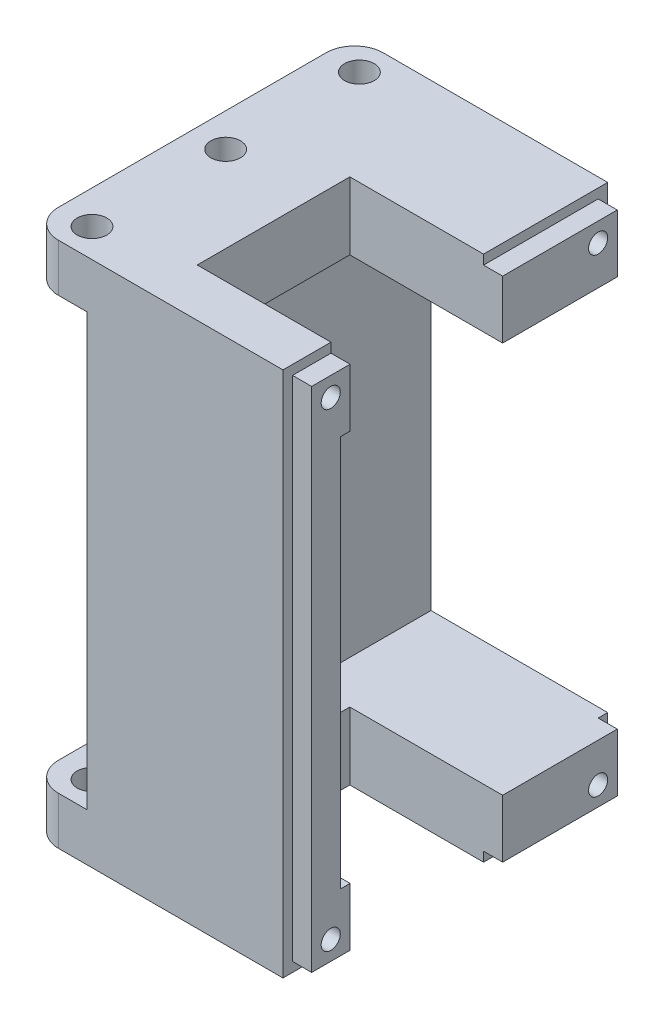
SolidWorks part; units mm, degrees
ref_plane "前视基准面" through (0, 0, 0) normal (0, 0, 1) x (1, 0, 0)
ref_plane "上视基准面" through (0, 0, 0) normal (0, 1, 0) x (1, 0, 0)
ref_plane "右视基准面" through (0, 0, 0) normal (1, 0, 0) x (0, 0, -1)
other "Configuration Table"
sketch "草图1" plane through (0, 0, 0) normal (0, 0, 1) x (1, 0, 0)
  line L0 (-1000, 0) -> (49000, 0) construction
  line L1 (-10.25, -20) -> (10.25, -20)
  line L2 (-10.25, -20) -> (-10.25, 20)
  line L3 (-10.25, 20) -> (10.25, 20)
  line L4 (10.25, -20) -> (10.25, 20)
  line L5 (-10.25, -20) -> (10.25, 20) construction
  line L6 (-10.25, 20) -> (10.25, -20) construction
  line L7 (-5, 15) -> (5, 15)
  line L8 (-5, 15) -> (-5, 25)
  line L9 (-5, 25) -> (5, 25)
  line L10 (5, 15) -> (5, 25)
  line L11 (-5, 15) -> (5, 25) construction
  line L12 (-5, 25) -> (5, 15) construction
  line L14 (-10.25, -35.1417) -> (10.25, -35.1417)
  line L15 (-10.25, -35.1417) -> (-10.25, 35.1417)
  line L16 (-10.25, 35.1417) -> (10.25, 35.1417)
  line L17 (10.25, -35.1417) -> (10.25, 35.1417)
  line L18 (-10.25, -35.1417) -> (10.25, 35.1417) construction
  line L19 (-10.25, 35.1417) -> (10.25, -35.1417) construction
  circle A0 centre (-5, 25) radius 2
  circle A1 centre (5, 25) radius 2
  circle A2 centre (5, -25) radius 2
  circle A3 centre (-5, -25) radius 2
  point P0 (0, 0)
  point P6 (0, 20)
  point P19 (0, 0)
  dimension "D5" = 4
  dimension "D6" = 4
  dimension "D1" = 20.5
  dimension "D2" = 40
  dimension "D3" = 10
  dimension "D4" = 10
extrude "凸台-拉伸1" add sketch "草图1" along normal blind 29 contours A1 L10 L3 L17 L16 L15 L8 A0 L9 | L14 L17 L1 L15 A2 A3 | A1 L9 A0 L8 L3 L10 region at (0, -27.7973, 0) region at (0, 28.799, 0) region at (0, 22.2627, 0)
sketch "草图2" plane through (0, 0, 29) normal (0, 0, 1) x (1, 0, 0)
  line L1 (-10.25, 35.1417) -> (10.25, 35.1417)
  line L2 (-10.25, 35.1417) -> (-10.25, -35.1417)
  line L3 (-10.25, -35.1417) -> (10.25, -35.1417)
  line L4 (10.25, 35.1417) -> (10.25, -35.1417)
extrude "凸台-拉伸2" add sketch "草图2" along normal blind 3
sketch "草图3" plane through (0, 0, 0) normal (0, 0, -1) x (-1, 0, 0)
  line L0 (-10.25, -35.1417) -> (-10.25, -20) construction
  line L1 (-10.25, -27.5709) -> (10.25, -27.5709)
  line L2 (-10.25, -27.5709) -> (-10.25, 27.5709)
  line L3 (-10.25, 27.5709) -> (10.25, 27.5709)
  line L4 (10.25, -27.5709) -> (10.25, 27.5709)
  line L5 (10.25, 20) -> (10.25, 35.1417) construction
  line L7 (-10.25, -35.1417) -> (10.25, -35.1417)
  line L8 (-10.25, -35.1417) -> (-10.25, 35.1417)
  line L9 (-10.25, 35.1417) -> (10.25, 35.1417)
  line L10 (10.25, -35.1417) -> (10.25, 35.1417)
  line M2 (-10.25, -35.1417) -> (10.25, -35.1417)
  line M3 (10.25, -35.1417) -> (10.25, -20)
  line M5 (-10.25, -20) -> (-10.25, -35.1417)
extrude "切除-拉伸1" cut sketch "草图3" against normal through all contours L1 M5 M2 M3 | L3 L10 L9 L8 region at (0, -31.3563, 0) region at (0, 31.3563, 0)
sketch "草图5" plane through (0, -27.5709, 0) normal (0, -1, 0) x (1, 0, 0)
  line L0 (0, 0) -> (0, 2.5)
  circle A0 centre (0, 2.5) radius 2.5
  dimension "D2" = 5
  dimension "D1" = 2.5
extrude "凸台-拉伸3" add sketch "草图5" along normal blind 10 contours A0 region at (1.7178, -27.5709, 0.7822)
sketch "草图8" plane through (0, 27.5709, 0) normal (0, 1, 0) x (1, 0, 0)
  line L0 (0, 0) -> (0, -2.5)
  line L1 (0, -2.5) -> (0, -16.5)
  line L2 (0, -16.5) -> (0, -26.5)
  circle A0 centre (0, -16.5) radius 1.6
  circle A1 centre (0, -26.5) radius 1.6
  dimension "D4" = 3.2
  dimension "D5" = 3.2
  dimension "D1" = 2.5
  dimension "D2" = 14
  dimension "D3" = 10
extrude "切除-拉伸2" cut sketch "草图8" against normal up to next contours L1 A0 L2 | L2 A0 L1 | A1 region at (0.6791, 27.5709, 16.5) region at (1.0994, 27.5709, 25.4006) region at (-0.6791, 27.5709, 16.5)
sketch "草图9" plane through (0, -27.5709, 0) normal (0, -1, 0) x (1, 0, 0)
  line L1 (-10.25, 32) -> (10.25, 32)
  line L2 (-10.25, 32) -> (-10.25, 0)
  line L3 (-10.25, 0) -> (10.25, 0)
  line L4 (10.25, 32) -> (10.25, 0)
extrude "切除-拉伸3" cut sketch "草图9" along normal through all
sketch "草图12" plane through (0, 0, 0) normal (0, 0, -1) x (-1, 0, 0)
  line L1 (-10.25, 27.5709) -> (10.25, 27.5709)
  line L2 (-10.25, 27.5709) -> (-10.25, 20)
  line L3 (-10.25, 20) -> (10.25, 20)
  line L4 (10.25, 27.5709) -> (10.25, 20)
  circle A0 centre (-5, 25) radius 2
  circle A1 centre (5, 25) radius 2
extrude "凸台-拉伸5" add sketch "草图12" against normal blind 30
sketch "草图13" plane through (0, 27.5709, 0) normal (0, 1, 0) x (1, 0, 0)
  line L0 (0, 0) -> (0, -32)
  line L1 (10.25, -32) -> (-10.25, -32) construction
  line L2 (0, 0) -> (0, -10)
  line L3 (0, 0) -> (0, -2.5275)
  line L4 (0, 0) -> (0, -5)
  circle A2 centre (0, -5) radius 2.5
  circle A3 centre (0, -5) radius 4
  dimension "D3" = 5
  dimension "D4" = 5
  dimension "D5" = 8
  dimension "D1" = 32
  dimension "D2" = 10
extrude "凸台-拉伸6" add sketch "草图13" along normal blind 10 contours L4 A3 L2 A2 | L2 A3 L4 A2 region at (-2.5894, 27.5709, 5) region at (0.0894, 27.5709, 1.75)
sketch "草图15" plane through (0, 0, 0) normal (1, 0, 0) x (0, 0, -1)
  line L0 (-1, 27.5709) -> (0, 27.5709)
  line L1 (-1, 27.5709) -> (-1, 28.676)
  line L2 (-1, 27.5709) -> (-1, 37.5709) construction
  line L3 (-5, -962.4291) -> (-5, 49037.5709) construction
  line L4 (-2.5, 37.5709) -> (-7.5, 37.5709) construction
  arc A0 (-1, 28.676) -> (0, 27.5709) centre (0.1107, 28.676) ccw
  point P13 (-5, 37.5709)
revolve "旋转1" add sketch "草图15" angle 360 about L3
ref_plane "基准面1" through (0, 0, 5) normal (0, 0, 1) x (1, 0, 0)
sketch "草图16" plane through (0, 0, 5) normal (0, 0, 1) x (1, 0, 0)
  line L0 (0, 37.5709) -> (0, 33.5709)
  line L1 (2.5, 37.5709) -> (-2.5, 37.5709) construction
  circle A0 centre (0, 33.5709) radius 1.5
  dimension "D2" = 3
  dimension "D1" = 4
extrude "切除-拉伸5" cut sketch "草图16" against normal through all contours A0 region at (-1.0307, 32.5402, 5)
sketch "草图17" plane through (0, 0, 0) normal (1, 0, 0) x (0, 0, -1)
  line L0 (-5, 37.5709) -> (-5, 33.5709)
  line L1 (-2.5, 37.5709) -> (-7.5, 37.5709) construction
  line L2 (-5, 11.275) -> (-5, -11.275) construction
  circle A0 centre (-5, 33.5709) radius 1.5
  dimension "D2" = 3
  dimension "D1" = 4
extrude "切除-拉伸6" cut sketch "草图17" against normal through all contours A0 region at (0, 32.5402, 6.0307)
sketch "草图19" plane through (0, -27.5709, 0) normal (0, -1, 0) x (1, 0, 0)
  line L0 (0, 0) -> (0, 5)
  line L1 (10.25, 0) -> (-10.25, 0) construction
  circle A0 centre (0, 5) radius 2.5
  circle A1 centre (0, 5) radius 4
  dimension "D2" = 5
  dimension "D3" = 8
  dimension "D1" = 5
extrude "凸台-拉伸7" add sketch "草图19" along normal blind 10 contours A1 A0 region at (-2.7484, -27.5709, 7.7484)
sketch "草图20" plane through (0, 0, 0) normal (1, 0, 0) x (0, 0, -1)
  line L0 (-1, -27.5709) -> (0, -27.5709)
  line L1 (-1, -27.5709) -> (-1, -28.5709)
  line L2 (-1, -37.5709) -> (-1, -27.5709) construction
  line L3 (-5, -1027.5709) -> (-5, 48972.4291) construction
  line L4 (-9, -27.5709) -> (-1, -27.5709) construction
  arc A0 (-1, -28.5709) -> (0, -27.5709) centre (0, -28.5709) cw
  point P13 (-5, -27.5709)
  dimension "D1" = 1
revolve "旋转2" add sketch "草图20" angle 360 about L3
sketch "草图21" plane through (0, 0, 5) normal (0, 0, 1) x (1, 0, 0)
  line L0 (0, -37.5709) -> (0, -33.5709)
  line L1 (-4, -37.5709) -> (4, -37.5709) construction
  circle A0 centre (0, -33.5709) radius 1.5
  dimension "D2" = 3
  dimension "D1" = 4
extrude "切除-拉伸7" cut sketch "草图21" against normal through all contours A0 region at (1.0307, -34.6015, 5)
sketch "草图22" plane through (0, 0, 0) normal (1, 0, 0) x (0, 0, -1)
  line L0 (-5, -37.5709) -> (-5, -33.5709)
  line L1 (-9, -37.5709) -> (-1, -37.5709) construction
  line L2 (-5, 11.275) -> (-5, -11.275) construction
  circle A0 centre (-5, -33.5709) radius 1.5
  dimension "D2" = 3
  dimension "D1" = 4
extrude "切除-拉伸8" cut sketch "草图22" against normal through all contours A0 region at (0, -34.6015, 3.9693)
sketch "草图23" plane through (0, 0, 32) normal (0, 0, 1) x (1, 0, 0)
  line L1 (-10.25, 27.5709) -> (10.25, 27.5709)
  line L2 (-10.25, 27.5709) -> (-10.25, -27.5709)
  line L3 (-10.25, -27.5709) -> (10.25, -27.5709)
  line L4 (10.25, 27.5709) -> (10.25, -27.5709)
extrude "凸台-拉伸8" add sketch "草图23" along normal blind 2
sketch "草图24" plane through (-10.25, 0, 0) normal (-1, 0, 0) x (0, 0, 1)
  line L0 (34, -27.5709) -> (0, -27.5709) construction
  line L1 (34, 27.5709) -> (24, 27.5709)
  line L2 (34, 27.5709) -> (34, -27.5709)
  line L3 (34, -27.5709) -> (24, -27.5709)
  line L4 (24, 27.5709) -> (24, -27.5709)
  dimension "D1" = 10
extrude "凸台-拉伸9" add sketch "草图24" along normal blind 2
sketch "草图25" plane through (10.25, 0, 0) normal (1, 0, 0) x (0, 0, -1)
  line L0 (-34, 27.5709) -> (-21, 27.5709)
  line L1 (-34, 27.5709) -> (0, 27.5709) construction
  line L2 (-21, 27.5709) -> (-17, 27.5709)
  line L3 (-17, 27.5709) -> (-17, -27.5709)
  line L6 (-17, -27.5709) -> (-25, -27.5709)
  line L7 (-34, -27.5709) -> (0, -27.5709) construction
  line L8 (-25, -27.5709) -> (-25, 27.5709)
  line M5 (-29, 20) -> (0, 20)
  line M7 (0, 27.5709) -> (-34, 27.5709)
  line M9 (-34, -27.5709) -> (0, -27.5709)
  line M11 (0, -20) -> (-29, -20)
  dimension "D1" = 13
  dimension "D2" = 4
  dimension "D3" = 8
extrude "切除-拉伸9" cut sketch "草图25" against normal blind 16 contours L8 L3 M9 M11 | L8 L3 M5 M7 region at (10.25, 23.7854, 21) region at (10.25, -23.7854, 21)
sketch "草图26" plane through (0, 0, 29) normal (0, 0, -1) x (-1, 0, 0)
  circle A0 centre (-5, 25) radius 2
  circle A1 centre (5, 25) radius 2
  circle A2 centre (-5, -25) radius 2
  circle A3 centre (5, -25) radius 2
extrude "凸台-拉伸10" add sketch "草图26" along normal blind 20
sketch "草图27" plane through (0, -27.5709, 0) normal (0, -1, 0) x (1, 0, 0)
  line L1 (-5.75, 25) -> (10.25, 25)
  line L2 (-5.75, 25) -> (-5.75, 17)
  line L3 (-5.75, 17) -> (10.25, 17)
  line L4 (10.25, 25) -> (10.25, 17)
extrude "切除-拉伸10" cut sketch "草图27" against normal through all
sketch "草图29" plane through (10.25, 0, 0) normal (1, 0, 0) x (0, 0, -1)
  line L0 (-33, 26.5709) -> (-33, -26.5709)
  line L1 (-34, 27.5709) -> (0, 27.5709)
  line L2 (-34, 27.5709) -> (-34, -27.5709)
  line L3 (-34, -27.5709) -> (0, -27.5709)
  line L4 (0, 27.5709) -> (0, -27.5709)
  line L5 (-33, -26.5709) -> (-1, -26.5709)
  line L6 (-1, 26.5709) -> (-1, -26.5709)
  line L7 (-33, 26.5709) -> (-1, 26.5709)
  dimension "D1" = 1
extrude "切除-拉伸11" cut sketch "草图29" against normal blind 2
sketch "草图30" plane through (10.25, 0, 0) normal (1, 0, 0) x (0, 0, -1)
  line L1 (-34, 27.5709) -> (0, 27.5709)
  line L2 (-34, 27.5709) -> (-34, -27.5709)
  line L3 (-34, -27.5709) -> (0, -27.5709)
  line L4 (0, 27.5709) -> (0, -27.5709)
  dimension "D1" = 34
  dimension "D2" = 55.1417
sketch "草图32" plane through (10.25, 0, 0) normal (1, 0, 0) x (0, 0, -1)
  line L0 (-17, -26.5709) -> (-1, -26.5709) construction
  line L1 (-33, 26.5709) -> (-13, 26.5709)
  line L2 (-33, 26.5709) -> (-33, -26.5709)
  line L3 (-33, -26.5709) -> (-13, -26.5709)
  line L4 (-13, 26.5709) -> (-13, -26.5709)
  line L6 (-13, 26.5709) -> (-28.9769, 26.5709)
  line L7 (-13, 26.5709) -> (-13, -26.5709)
  line L8 (-13, -26.5709) -> (-28.9769, -26.5709)
  line L9 (-28.9769, 26.5709) -> (-28.9769, -26.5709)
  line L10 (-13, -26.5709) -> (-28.9769, -26.5709)
  line L11 (-13, -26.5709) -> (-13, 27.5939)
  line L12 (-13, 27.5939) -> (-28.9769, 27.5939)
  line L13 (-28.9769, -26.5709) -> (-28.9769, 27.5939)
  line L14 (-28.9769, 27.5939) -> (-13, 27.5939)
  line L15 (-28.9769, 27.5939) -> (-28.9769, -27.5919)
  line L16 (-28.9769, -27.5919) -> (-13, -27.5919)
  line L17 (-13, 27.5939) -> (-13, -27.5919)
  line M2 (-25, 26.5709) -> (-33, 26.5709)
  line M5 (-25, -26.5709) -> (-25, -20)
  line M6 (-25, -20) -> (-29, -20)
  line M8 (-29, 20) -> (-25, 20)
  line M9 (-25, 20) -> (-25, 26.5709)
  dimension "D1" = 20
extrude "切除-拉伸13" cut sketch "草图32" against normal blind 16 contours L9 L3 L4 L1 M8 M6 M5 M9 | L9 M2 M8 M9 | L9 L3 M6 M5 | L17 L3 L15 L16 | L13 L1 L11 L12 M2 region at (10.25, 27.0824, 20.9884) region at (10.25, 23.2854, 26.9884) region at (10.25, 0, 20.5949) region at (10.25, -23.2854, 26.9884) region at (10.25, -27.0814, 20.9884)
sketch "草图33" plane through (10.25, 0, 0) normal (1, 0, 0) x (0, 0, -1)
  line L1 (-33, 26.5709) -> (-31, 26.5709)
  line L2 (-33, 26.5709) -> (-33, 24.5709)
  line L3 (-33, 24.5709) -> (-31, 24.5709)
  line L4 (-31, 26.5709) -> (-31, 24.5709)
  line L5 (-33, -26.5709) -> (-31, -26.5709)
  line L6 (-33, -26.5709) -> (-33, -24.5709)
  line L7 (-33, -24.5709) -> (-31, -24.5709)
  line L8 (-31, -26.5709) -> (-31, -24.5709)
  circle A0 centre (-31, 24.5709) radius 1
  circle A1 centre (-31, -24.5709) radius 1
  dimension "D3" = 2
  dimension "D6" = 2
  dimension "D1" = 2
  dimension "D2" = 2
  dimension "D4" = 2
  dimension "D5" = 2
extrude "切除-拉伸14" cut sketch "草图33" against normal blind 16 contours A1 | A0
sketch "草图35" plane through (10.25, 0, 0) normal (1, 0, 0) x (0, 0, -1)
  line L1 (-1, 26.5709) -> (-3, 26.5709)
  line L2 (-1, 26.5709) -> (-1, 24.5709)
  line L3 (-1, 24.5709) -> (-3, 24.5709)
  line L4 (-3, 26.5709) -> (-3, 24.5709)
  line L5 (-1, -26.5709) -> (-3, -26.5709)
  line L6 (-1, -26.5709) -> (-1, -24.5709)
  line L7 (-1, -24.5709) -> (-3, -24.5709)
  line L8 (-3, -26.5709) -> (-3, -24.5709)
  circle A0 centre (-3, 24.5709) radius 1
  circle A1 centre (-3, -24.5709) radius 1
  dimension "D3" = 2
  dimension "D6" = 2
  dimension "D1" = 2
  dimension "D2" = 2
  dimension "D4" = 2
  dimension "D5" = 2
extrude "切除-拉伸15" cut sketch "草图35" against normal blind 5 contours A1 | A0
sketch "草图36" plane through (0, -37.5709, 0) normal (0, -1, 0) x (1, 0, 0)
  circle A1 centre (0, 5) radius 2.65
  dimension "D1" = 5.3
extrude "切除-拉伸16" cut sketch "草图36" against normal blind 10
sketch "草图37" plane through (0, 37.5709, 0) normal (0, 1, 0) x (1, 0, 0)
  circle A0 centre (0, -5) radius 2.65
  dimension "D1" = 5.3
extrude "切除-拉伸17" cut sketch "草图37" against normal blind 10
sketch "草图38" plane through (0, -27.5709, 0) normal (0, -1, 0) x (1, 0, 0)
  line L1 (-28.75, -34) -> (8.25, -34)
  line L2 (-28.75, -34) -> (-28.75, 34)
  line L3 (-28.75, 34) -> (8.25, 34)
  line L4 (8.25, -34) -> (8.25, 34)
  line L5 (-28.75, -34) -> (8.25, 34) construction
  line L6 (-28.75, 34) -> (8.25, -34) construction
  point P0 (-10.25, 0)
extrude "切除-拉伸18" cut sketch "草图38" along normal blind 10
sketch "草图39" plane through (-10.25, 0, 0) normal (-1, 0, 0) x (0, 0, 1)
  line L1 (0, 27.5709) -> (24, 27.5709)
  line L2 (0, 27.5709) -> (0, -27.5709)
  line L3 (0, -27.5709) -> (24, -27.5709)
  line L4 (24, 27.5709) -> (24, -27.5709)
extrude "凸台-拉伸11" add sketch "草图39" along normal blind 2
sketch "草图40" plane through (0, 27.5709, 0) normal (0, 1, 0) x (1, 0, 0)
  line L1 (-12.25, 0) -> (8.25, 0)
  line L2 (-12.25, 0) -> (-12.25, -34)
  line L3 (-12.25, -34) -> (8.25, -34)
  line L4 (8.25, 0) -> (8.25, -34)
extrude "切除-拉伸19" cut sketch "草图40" along normal through all
sketch "草图41" plane through (0, 27.5709, 0) normal (0, 1, 0) x (1, 0, 0)
  line L1 (-12.25, 0) -> (-17.25, 0)
  line L2 (-12.25, 0) -> (-12.25, -34)
  line L3 (-12.25, -34) -> (-17.25, -34)
  line L4 (-17.25, 0) -> (-17.25, -34)
  dimension "D1" = 5
  dimension "D2" = 34
extrude "凸台-拉伸12" add sketch "草图41" against normal blind 5
mirror "镜向1" about plane through (0, 0, 0) normal (0, 1, 0) of "凸台-拉伸12"
sketch "草图42" plane through (0, -27.5709, 0) normal (0, -1, 0) x (1, 0, 0)
  line L0 (-17.25, 34) -> (-14.75, 34)
  line L1 (-17.25, 34) -> (8.25, 34) construction
  line L2 (-14.75, 34) -> (-14.75, 31)
  line L3 (-1017.25, 17) -> (48982.75, 17) construction
  line L4 (-19.75, -3) -> (-14.75, -3)
  line L5 (-19.75, -3) -> (-19.75, 3)
  line L6 (-19.75, 3) -> (-14.75, 3)
  line L7 (-14.75, -3) -> (-14.75, 3)
  line L8 (-19.75, -3) -> (-14.75, 3) construction
  line L9 (-19.75, 3) -> (-14.75, -3) construction
  line L10 (-17.25, 0) -> (-17.25, 34) construction
  line L11 (-17.25, 17) -> (-14.75, 17)
  circle A0 centre (-14.75, 31) radius 2
  circle A1 centre (-14.75, 3) radius 2
  circle A2 centre (-14.75, 17) radius 2
  point P7 (-17.25, 0)
  point P19 (-17.25, 17)
  dimension "D3" = 4
  dimension "D6" = 4
  dimension "D8" = 4
  dimension "D1" = 2.5
  dimension "D2" = 3
  dimension "D4" = 6
  dimension "D5" = 5
  dimension "D7" = 2.5
extrude "切除-拉伸20" cut sketch "草图42" against normal through all contours L7 A1 L6 | A2 | A0 | A1 region at (-14.4671, -27.5709, 3.2829) region at (-16.1242, -27.5709, 29.6258) region at (-14.75, -27.5709, 15.0566)
sketch "草图43" plane through (0, -27.5709, 0) normal (0, -1, 0) x (1, 0, 0)
  line L1 (-17.25, 34) -> (-18.25, 34)
  line L2 (-17.25, 34) -> (-17.25, 0)
  line L3 (-17.25, 0) -> (-18.25, 0)
  line L4 (-18.25, 34) -> (-18.25, 0)
  dimension "D1" = 1
extrude "凸台-拉伸13" add sketch "草图43" against normal blind 5
sketch "草图44" plane through (-17.25, 0, 0) normal (-1, 0, 0) x (0, 0, 1)
  line L1 (0, 27.5709) -> (34, 27.5709)
  line L2 (0, 27.5709) -> (0, 22.5709)
  line L3 (0, 22.5709) -> (34, 22.5709)
  line L4 (34, 27.5709) -> (34, 22.5709)
extrude "凸台-拉伸14" add sketch "草图44" along normal blind 1
sketch "草图45" plane through (0, 27.5709, 0) normal (0, 1, 0) x (1, 0, 0)
  circle A0 centre (-14.75, -3) radius 2
  circle A1 centre (-14.75, -17) radius 2
  circle A2 centre (-14.75, -31) radius 2
  circle A3 centre (-14.75, -3) radius 1.55
  circle A4 centre (-14.75, -17) radius 1.55
  circle A5 centre (-14.75, -31) radius 1.55
  dimension "D1" = 3.1
  dimension "D2" = 3.1
  dimension "D3" = 3.1
extrude "凸台-拉伸15" add sketch "草图45" against normal blind 5
sketch "草图46" plane through (0, -27.5709, 0) normal (0, -1, 0) x (1, 0, 0)
  circle A0 centre (-14.75, 31) radius 2
  circle A1 centre (-14.75, 31) radius 1.55
  circle A2 centre (-14.75, 17) radius 2
  circle A3 centre (-14.75, 17) radius 1.55
  circle A4 centre (-14.75, 3) radius 2
  circle A5 centre (-14.75, 3) radius 1.55
extrude "凸台-拉伸16" add sketch "草图46" against normal blind 5
fillet "圆角1" radius 3 1 edges at (-18.25, -25.0709, 0) type face fillet first side face at (-18.25, -25.0709, 17) second side face at (-3, 25, 0)
fillet "圆角2" radius 3 1 edges at (-18.25, -25.0709, 34) type face fillet first side face at (-18.25, -25.0709, 18.5) second side face at (-10.125, 0, 34)
fillet "圆角3" radius 3 1 edges at (-18.25, 25.0709, 0) type face fillet first side face at (-18.25, 25.0709, 17) second side face at (-3, 25, 0)
fillet "圆角4" radius 3 1 edges at (-18.25, 25.0709, 34) type face fillet first side face at (-18.25, 25.0709, 18.5) second side face at (-9.375, 0, 34)
sketch "草图47" plane through (0, 0, 0) normal (0, 0, -1) x (-1, 0, 0)
  circle A0 centre (-5, 25) radius 2
  circle A1 centre (5, 25) radius 2
  circle A2 centre (-5, -25) radius 2
  circle A3 centre (5, -25) radius 2
extrude "凸台-拉伸17" add sketch "草图47" against normal blind 10
sketch "草图48" plane through (0, 0, 0) normal (0, 0, -1) x (-1, 0, 0)
  line L0 (0, -1000) -> (0, 49000) construction
  line L1 (-10, -20) -> (10, -20)
  line L2 (-10, -20) -> (-10, 20)
  line L3 (-10, 20) -> (10, 20)
  line L4 (10, -20) -> (10, 20)
  line L5 (-10, -20) -> (10, 20) construction
  line L6 (-10, 20) -> (10, -20) construction
  line L7 (0, 20) -> (0, 24.5)
  line L8 (0, 24.5) -> (-5, 24.5)
  line L9 (-1000, 0) -> (49000, 0) construction
  circle A0 centre (-5, 24.5) radius 2
  circle A1 centre (5, 24.5) radius 2
  circle A2 centre (5, -24.5) radius 2
  circle A3 centre (-5, -24.5) radius 2
  point P0 (0, 0)
  dimension "D5" = 4
  dimension "D1" = 20
  dimension "D2" = 40
  dimension "D3" = 4.5
  dimension "D4" = 5
extrude "切除-拉伸21" cut sketch "草图48" against normal blind 10 contours A2 | A3 | A1 | A0 region at (6.9434, 24.5, 0) region at (-5, 24.5, 0) region at (-5, -24.5, 0) region at (5, -24.5, 0)
sketch "草图49" plane through (0, 0, 0) normal (0, 0, -1) x (-1, 0, 0)
  line L1 (-10.25, -20.5) -> (10.25, -20.5)
  line L2 (-10.25, -20.5) -> (-10.25, 20.5)
  line L3 (-10.25, 20.5) -> (10.25, 20.5)
  line L4 (10.25, -20.5) -> (10.25, 20.5)
  line L5 (-10.25, -20.5) -> (10.25, 20.5) construction
  line L6 (-10.25, 20.5) -> (10.25, -20.5) construction
  point P0 (0, 0)
  dimension "D1" = 41
extrude "切除-拉伸23" cut sketch "草图49" against normal blind 30
